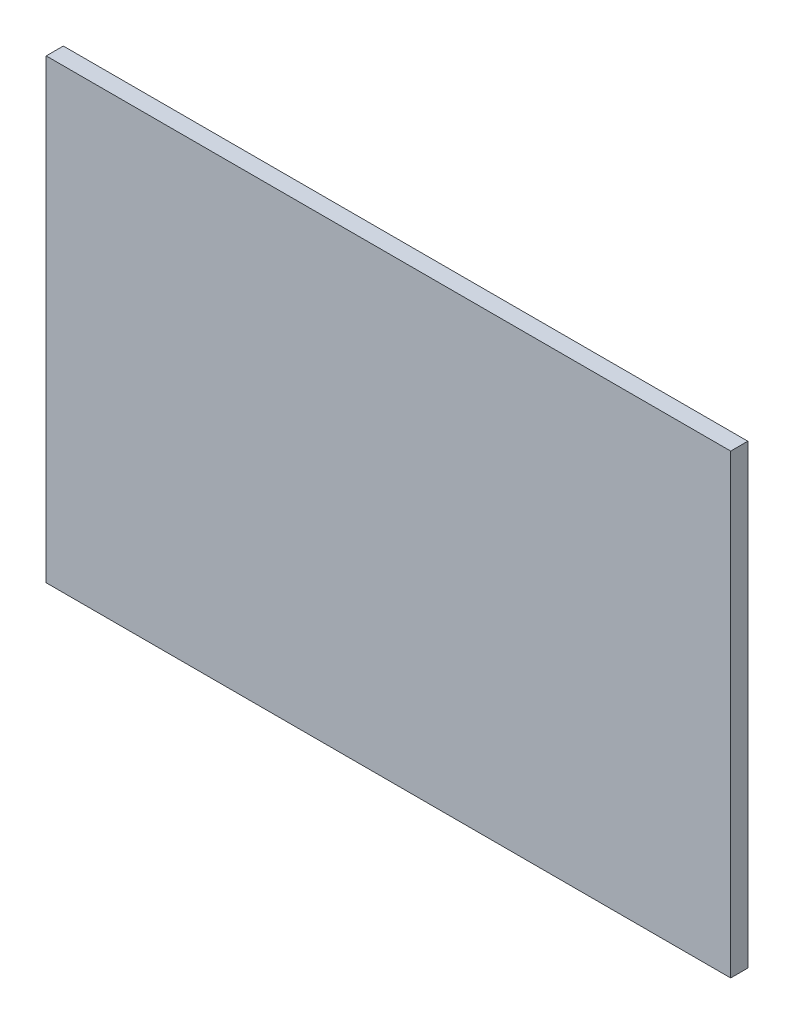
SolidWorks part; units mm, degrees
material "Лист 3,0 ГОСТ 19903-2015 / Ст3сп ГОСТ 14637-89"
ref_plane "Спереди" through (0, 0, 0) normal (0, 0, 1) x (1, 0, 0)
ref_plane "Сверху" through (0, 0, 0) normal (0, 1, 0) x (1, 0, 0)
ref_plane "Справа" through (0, 0, 0) normal (1, 0, 0) x (0, 0, -1)
sketch "Эскиз1" plane through (0, 0, 0) normal (0, 0, 1) x (1, 0, 0)
  line L1 (-60, -40) -> (60, -40)
  line L2 (-60, -40) -> (-60, 40)
  line L3 (-60, 40) -> (60, 40)
  line L4 (60, -40) -> (60, 40)
base flange "Базовая кромка1" sketch "Эскиз1" thickness 3 reverse thickness direction no parameters "D1"=3
sketch "Сгиб-Линии1" [suppressed] plane through (0, 0, 0) normal (0, 1, 0) x (1, 0, 0)
sketch "Граничная рамка1" [suppressed] plane through (0, 0, 0) normal (0, 1, 0) x (1, 0, 0)
sheet metal parameters "Листовой металл30" thickness 3 parameters "D1"=3
flat pattern "Развертка30" [suppressed]
sketch "Сгиб-Линии2" plane through (0, 0, 0) normal (0, 1, 0) x (1, 0, 0)
sketch3d "Граничная рамка2" [suppressed]
  line L0 (60, -40, 0) -> (-60, -40, 0) construction
  line L1 (60, 40, 0) -> (-60, 40, 0) construction
  line L2 (60, -40, 0) -> (60, 40, 0) construction
  line L3 (-60, -40, 0) -> (-60, 40, 0) construction
